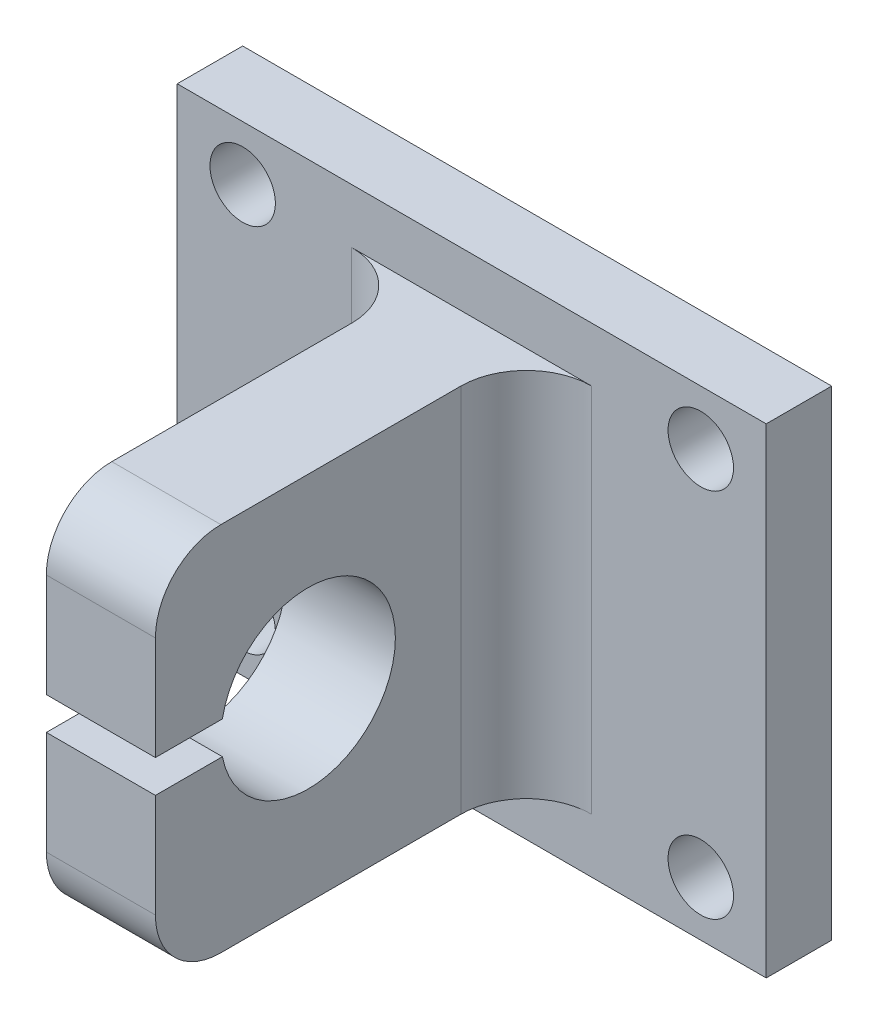
SolidWorks part; units mm, degrees
ref_plane "Front Plane" through (0, 0, 0) normal (0, 0, 1) x (1, 0, 0)
ref_plane "Top Plane" through (0, 0, 0) normal (0, 1, 0) x (1, 0, 0)
ref_plane "Right Plane" through (0, 0, 0) normal (1, 0, 0) x (0, 0, -1)
sketch "Sketch1" plane through (0, 0, 0) normal (0, 0, 1) x (1, 0, 0)
  line L1 (-13.5, -11) -> (13.5, -11)
  line L2 (-13.5, -11) -> (-13.5, 11)
  line L3 (-13.5, 11) -> (13.5, 11)
  line L4 (13.5, -11) -> (13.5, 11)
  line L5 (-13.5, -11) -> (13.5, 11) construction
  line L6 (-13.5, 11) -> (13.5, -11) construction
  line L7 (10.5, 8.5) -> (10.5, -8.5) construction
  line L8 (10.5, -8.5) -> (-10.5, -8.5) construction
  circle A2 centre (10.5, 8.5) radius 1.5
  circle A3 centre (10.5, -8.5) radius 1.5
  circle A4 centre (-10.5, -8.5) radius 1.5
  circle A5 centre (-10.5, 8.5) radius 1.5
  point P0 (0, 0)
  point P21 (0, -8.5)
  point P22 (0, -11)
  point P23 (10.5, 0)
  point P24 (13.5, 0)
  dimension "D5" = 3
  dimension "D1" = 27
  dimension "D2" = 22
  dimension "D6" = 17
  dimension "D7" = 21
extrude "Boss-Extrude1" add sketch "Sketch1" along normal blind 3
sketch "Sketch2" plane through (0, 0, 3) normal (0, 0, 1) x (1, 0, 0)
  line L1 (-2.5, 8.5) -> (2.5, 8.5)
  line L2 (-2.5, 8.5) -> (-2.5, -8.5)
  line L3 (-2.5, -8.5) -> (2.5, -8.5)
  line L4 (2.5, 8.5) -> (2.5, -8.5)
  line L5 (-13.5, -11) -> (13.5, -11) construction
  line L6 (2.5, 6.1093) -> (-2.5, 6.1093) construction
  line L7 (13.5, -11) -> (13.5, 11) construction
  point P10 (0, -11)
  point P11 (0, 6.1093)
  point P14 (13.5, 0)
  point P15 (2.5, 0)
  dimension "D1" = 5
  dimension "D2" = 17
extrude "Boss-Extrude2" add sketch "Sketch2" along normal blind 17
sketch "Sketch3" plane through (2.5, 0, 0) normal (1, 0, 0) x (0, 0, -1)
  line L0 (-20, -8.5) -> (-20, 8.5) construction
  line L1 (-3, -8.5) -> (-3, 8.5) construction
  circle A0 centre (-13, 0) radius 4
  point P5 (-20, 0)
  dimension "D1" = 8
  dimension "D2" = 10
extrude "Cut-Extrude1" cut sketch "Sketch3" against normal through all both and the other way through all
sketch "Sketch4" plane through (2.5, 0, 0) normal (1, 0, 0) x (0, 0, -1)
  line L1 (-22.3796, -0.75) -> (-14.282, -0.75)
  line L2 (-22.3796, -0.75) -> (-22.3796, 0.75)
  line L3 (-22.3796, 0.75) -> (-14.282, 0.75)
  line L4 (-14.282, -0.75) -> (-14.282, 0.75)
  line L5 (-20, -8.5) -> (-20, 8.5) construction
  point P6 (-20, 0)
  point P7 (-22.3796, 0)
  dimension "D1" = 1.5
extrude "Cut-Extrude2" cut sketch "Sketch4" against normal through all both and the other way through all
fillet "Fillet1" radius 3 2 edges at (-2.5, 0, 3) (2.5, 0, 3)
fillet "Fillet2" radius 3 2 edges at (0, 8.5, 20) (0, -8.5, 20)
